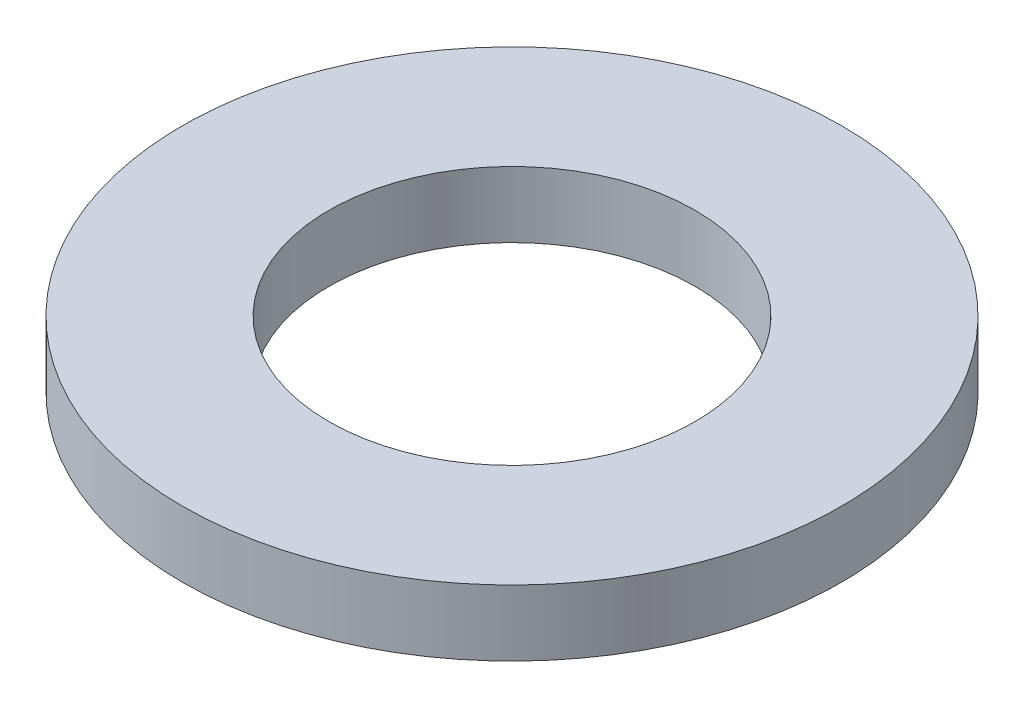
SolidWorks part; units mm, degrees
ref_plane "Front Plane" through (0, 0, 0) normal (0, 0, 1) x (1, 0, 0)
ref_plane "Top Plane" through (0, 0, 0) normal (0, 1, 0) x (1, 0, 0)
ref_plane "Right Plane" through (0, 0, 0) normal (1, 0, 0) x (0, 0, -1)
sketch "Sketch1" plane through (0, 0, 0) normal (0, 1, 0) x (1, 0, 0)
  circle A0 centre (0, 0) radius 90
  dimension "FLANGE_OD" = 180
extrude "Boss-Extrude1" add sketch "Sketch1" along normal blind 18
sketch "Sketch2" plane through (0, 0, 0) normal (0, 1, 0) x (1, 0, 0)
  circle A0 centre (0, 0) radius 50
  dimension "BORE_D" = 100
extrude "Cut-Extrude1" cut sketch "Sketch2" along normal through all
sketch "Sketch3" plane through (0, 18, 0) normal (0, 1, 0) x (1, 0, 0)
  circle A0 centre (0, 0) radius 34.9193 construction
  circle A1 centre (-34.9193, 0) radius 5.4817
  dimension "BOLT_D" = 10.9634
  dimension "BOLT_PCD" = 69.8385
extrude "Cut-Extrude2" cut sketch "Sketch3" against normal blind 14.5846 rebuild error yes
pattern_circular "CirPattern1" count 6 over 360 rebuild error yes
